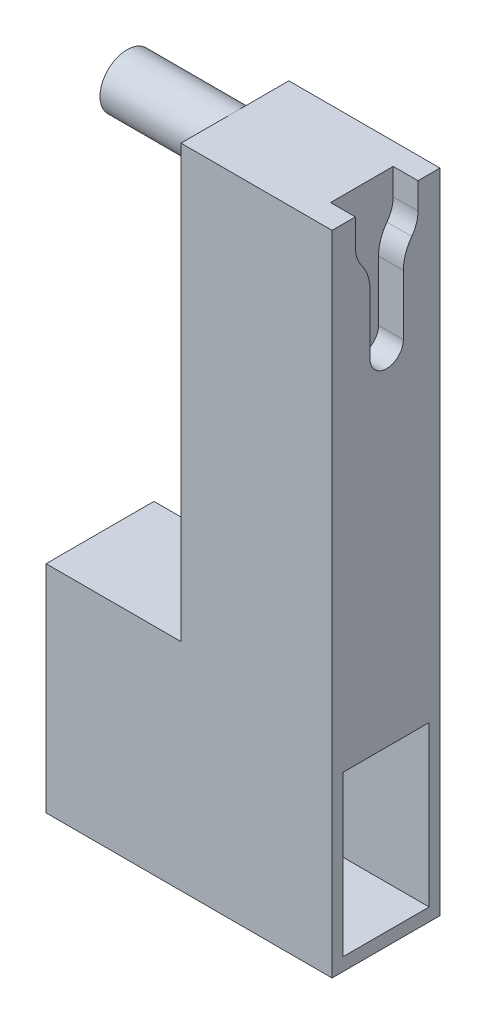
SolidWorks part; units mm, degrees
ref_plane "Front Plane" through (0, 0, 0) normal (0, 0, 1) x (1, 0, 0)
ref_plane "Top Plane" through (0, 0, 0) normal (0, 1, 0) x (1, 0, 0)
ref_plane "Right Plane" through (0, 0, 0) normal (1, 0, 0) x (0, 0, -1)
sketch "Sketch1" plane through (0, 0, 0) normal (0, 1, 0) x (1, 0, 0)
  line L1 (-17.78, -12.7) -> (17.78, -12.7)
  line L2 (-17.78, -12.7) -> (-17.78, 12.7)
  line L3 (-17.78, 12.7) -> (17.78, 12.7)
  line L4 (17.78, -12.7) -> (17.78, 12.7)
  line L5 (-17.78, -12.7) -> (17.78, 12.7) construction
  line L6 (-17.78, 12.7) -> (17.78, -12.7) construction
  point P0 (0, 0)
  dimension "D1" = 25.4
  dimension "D2" = 35.56
extrude "Boss-Extrude1" add sketch "Sketch1" along normal mid plane 50.8
sketch "Sketch2" plane through (-17.78, 0, 0) normal (-1, 0, 0) x (0, 0, 1)
  line L0 (-12.7, 25.4) -> (12.7, 25.4) construction
  circle A0 centre (0, 19.05) radius 6.35
  dimension "D1" = 12.7
extrude "Boss-Extrude2" add sketch "Sketch2" along normal mid plane 50.8
sketch "Sketch4" plane through (17.78, 0, 0) normal (1, 0, 0) x (0, 0, -1)
  line L0 (-3.64, 8.86) -> (-3.64, -5.29) construction
  line L1 (3.96, 8.86) -> (3.96, -5.29) construction
  line L2 (-3.64, 8.86) -> (-3.64, -5.29) construction
  line L3 (3.96, 8.86) -> (3.96, -5.29) construction
  line L4 (-3.767, 8.86) -> (-3.767, -5.29)
  line L5 (4.087, 8.86) -> (4.087, -5.29)
  line L6 (7.537, 19.21) -> (7.537, 26.587)
  line L7 (-7.217, 19.21) -> (-7.217, 26.587)
  line L8 (7.537, 26.587) -> (0.16, 26.587)
  line L9 (0.16, 26.587) -> (-7.217, 26.587)
  arc A0 (-3.64, 8.86) -> (-5.64, 14.86) centre (-13.64, 8.86) ccw construction
  arc A1 (-3.64, -5.29) -> (0.16, -9.09) centre (0.16, -5.29) ccw construction
  circle A2 centre (0.16, -1.29) radius 1.3954
  arc A3 (6.0616, 14.7838) -> (-5.7416, 14.7838) centre (0.16, 19.21) ccw
  circle A4 centre (0.16, -5.29) radius 1.3954
  arc A8 (6.8475, 16.41) -> (6.16, 23.2797) centre (0.16, 19.21) ccw construction
  arc A9 (-3.767, 8.86) -> (-5.7416, 14.7838) centre (-13.64, 8.86) ccw
  arc A10 (5.96, 14.86) -> (4.132, 10.7069) centre (13.96, 8.86) ccw construction
  arc A12 (-3.64, 8.86) -> (-5.64, 14.86) centre (-13.64, 8.86) ccw construction
  arc A13 (-3.64, -5.29) -> (3.96, -5.29) centre (0.16, -5.29) ccw construction
  arc A14 (-3.767, -5.29) -> (4.087, -5.29) centre (0.16, -5.29) ccw
  arc A15 (6.0616, 14.7838) -> (4.087, 8.86) centre (13.96, 8.86) ccw
  arc A20 (5.96, 14.86) -> (-5.64, 14.86) centre (0.16, 19.21) ccw construction
  arc A22 (5.96, 14.86) -> (3.96, 8.86) centre (13.96, 8.86) ccw construction
  point P5 (0.16, 26.587)
  line M5 (12.7, 25.4) -> (-12.7, 25.4)
  dimension "D1" = 0.127
extrude "Cut-Extrude1" cut sketch "Sketch4" against normal blind 5.842 contours A15 A3 A9 L4 A14 L5 M5 | A3 L6 L8 M5 | A3 L6 M5 | A3 L7 M5 | A3 L9 L7 M5 | A3 M5 region at (17.78, 11.0506, -0.16) region at (17.78, 23.9318, 6.2648) region at (17.78, 26.0609, 4.7948) region at (17.78, 25.8782, -0.16) region at (17.78, 26.0609, -5.1148) region at (17.78, 23.9318, -6.5848)
sketch "Sketch7" plane through (0, -25.4, 0) normal (0, -1, 0) x (1, 0, 0)
  line L1 (-17.78, 12.7) -> (17.78, 12.7)
  line L2 (-17.78, 12.7) -> (-17.78, -12.7)
  line L3 (-17.78, -12.7) -> (17.78, -12.7)
  line L4 (17.78, 12.7) -> (17.78, -12.7)
extrude "Boss-Extrude3" add sketch "Sketch7" along normal blind 101.6
extrude "Cut-Extrude2" cut sketch "Sketch4<4>" against normal blind 12.7 and the other way through all contours A2 | A4 region at (17.78, -1.29, -0.16) region at (17.78, -5.29, -0.16)
sketch "Sketch4<4>" plane through (17.78, 0, 0) normal (1, 0, 0) x (0, 0, -1) same geometry as "Sketch4"
sketch "Sketch10" plane through (-17.78, 0, 0) normal (-1, 0, 0) x (0, 0, 1)
  line L0 (12.7, 25.4) -> (12.7, -127) construction
  line L1 (-12.7, -127) -> (12.7, -127)
  line L2 (-12.7, -127) -> (-12.7, -76.2)
  line L3 (-12.7, -76.2) -> (12.7, -76.2)
  line L4 (12.7, -127) -> (12.7, -76.2)
  dimension "D1" = 50.8
extrude "Boss-Extrude4" add sketch "Sketch10" along normal blind 31.75
sketch "Sketch11" plane through (17.78, 0, 0) normal (1, 0, 0) x (0, 0, -1)
  line L0 (12.7, 25.4) -> (12.7, -127) construction
  line L1 (-12.7, -127) -> (12.7, -127)
  line L2 (-12.7, -127) -> (-12.7, -76.2)
  line L3 (-12.7, -76.2) -> (12.7, -76.2)
  line L4 (12.7, -127) -> (12.7, -76.2)
  line L5 (-10.16, -123.952) -> (-12.7, -127) construction
  line L6 (-10.16, -123.952) -> (10.16, -123.952)
  line L7 (-10.16, -123.952) -> (-10.16, -86.36)
  line L8 (-10.16, -86.36) -> (10.16, -86.36)
  line L9 (10.16, -123.952) -> (10.16, -86.36)
  line L10 (10.16, -123.952) -> (12.7, -127) construction
  dimension "D1" = 50.8
  dimension "D2" = 3.048
  dimension "D3" = 20.32
  dimension "D4" = 37.592
extrude "Cut-Extrude3" cut sketch "Sketch11" against normal blind 49.53 contours L6 L9 L8 L7 region at (17.78, -105.156, 0)
